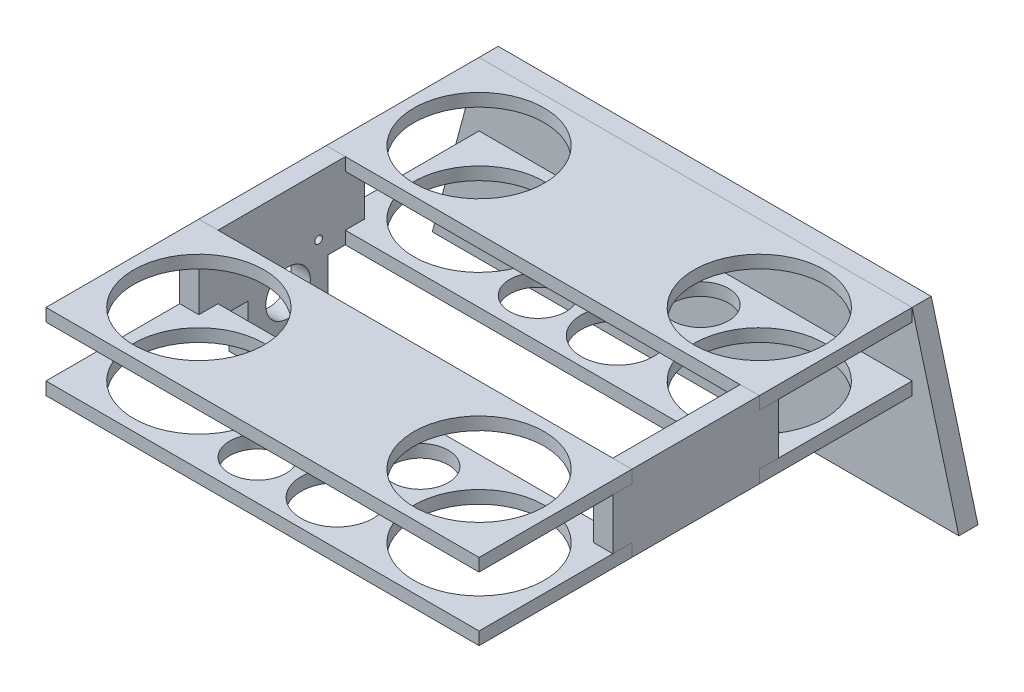
SolidWorks part; units mm, degrees
material "Alum Plate"
ref_plane "Front Plane" through (0, 0, 0) normal (0, 0, 1) x (1, 0, 0)
ref_plane "Top Plane" through (0, 0, 0) normal (0, 1, 0) x (1, 0, 0)
ref_plane "Right Plane" through (0, 0, 0) normal (1, 0, 0) x (0, 0, -1)
sketch "Sketch1" plane through (0, 0, 0) normal (0, 1, 0) x (1, 0, 0)
  line L0 (-69.85, 69.85) -> (-14.9491, 85.725) construction
  line L1 (107.95, -107.95) -> (-107.95, -107.95)
  line L2 (107.95, -107.95) -> (107.95, 107.95)
  line L3 (107.95, 107.95) -> (-107.95, 107.95)
  line L4 (-107.95, -107.95) -> (-107.95, 107.95)
  line L5 (107.95, -107.95) -> (-107.95, 107.95) construction
  line L6 (107.95, 107.95) -> (-107.95, -107.95) construction
  line L7 (-14.9491, 85.725) -> (-22.225, 51.5663) construction
  line L8 (-127, 0) -> (49.8373, 0) construction
  line L9 (0, 0) -> (0, 61.2225) construction
  line L10 (-107.95, 31.75) -> (107.95, 31.75) construction
  line L11 (-104.775, -14.825) -> (-47.625, -14.825)
  line L12 (-104.775, -14.825) -> (-104.775, 21.175)
  line L13 (-104.775, 21.175) -> (-47.625, 21.175)
  line L14 (-47.625, -14.825) -> (-47.625, 21.175)
  line L15 (-104.775, -14.825) -> (-47.625, 21.175) construction
  line L16 (-104.775, 21.175) -> (-47.625, -14.825) construction
  line L17 (-47.625, -10.825) -> (-0.635, -10.825)
  line L18 (-47.625, -10.825) -> (-47.625, 17.175)
  line L19 (-47.625, 17.175) -> (-0.635, 17.175)
  line L20 (-0.635, -10.825) -> (-0.635, 17.175)
  line L21 (-47.625, -10.825) -> (-0.635, 17.175) construction
  line L22 (-47.625, 17.175) -> (-0.635, -10.825) construction
  line L23 (-69.85, 31.75) -> (-69.85, 69.85) construction
  line L24 (-69.85, 69.85) -> (-69.85, 107.95) construction
  circle A0 centre (-69.85, 69.85) radius 32.5
  circle A1 centre (-14.9491, 85.725) radius 18
  circle A2 centre (-22.225, 51.5663) radius 14
  point P2 (0, 0)
  point P15 (-76.2, 3.175)
  point P21 (-69.85, 102.35)
  point P22 (-24.13, 3.175)
  point P27 (-69.85, 37.35)
  point P28 (-14.9491, 67.725)
  point P29 (-47.625, 3.175)
  point P30 (-14.9491, 103.725)
  point P31 (-22.225, 65.5663)
  point P32 (-22.225, 37.5663)
  point P37 (-76.2, 10.0231)
  dimension "D1" = 65
  dimension "D6" = 28
  dimension "D7" = 36
  dimension "D2" = 38.1
  dimension "D3" = 38.1
  dimension "D4" = 215.9
  dimension "D5" = 22.225
  dimension "D8" = 57.15
  dimension "D9" = 34.925
  dimension "D10" = 22.225
  dimension "D11" = 36
  dimension "D12" = 57.15
  dimension "D13" = 46.99
  dimension "D14" = 28
  dimension "D15" = 28.575
  dimension "D16" = 3.175
sketch "Sketch2" plane through (0, 0, 0) normal (1, 0, 0) x (0, 0, -1)
  line L0 (-200000, 0) -> (200061.2225, 0) construction
  line L1 (69.85, 50.8) -> (69.85, 53.975) construction
  line L2 (37.35, 60.975) -> (102.35, 60.975)
  line L3 (37.35, 60.975) -> (37.35, 53.975)
  line L4 (37.35, 53.975) -> (102.35, 53.975)
  line L5 (102.35, 60.975) -> (102.35, 53.975)
  line L6 (37.35, 60.975) -> (102.35, 53.975) construction
  line L7 (37.35, 53.975) -> (102.35, 60.975) construction
  line L8 (37.35, 92.075) -> (102.35, 92.075)
  line L9 (37.35, 92.075) -> (37.35, 85.075)
  line L10 (37.35, 85.075) -> (102.35, 85.075)
  line L11 (102.35, 92.075) -> (102.35, 85.075)
  line L12 (37.35, 92.075) -> (102.35, 85.075) construction
  line L13 (37.35, 85.075) -> (102.35, 92.075) construction
  line L14 (67.5868, 73.025) -> (88.6392, 73.025) construction
  line L15 (69.85, 60.975) -> (69.85, 73.025) construction
  line L16 (69.85, 73.025) -> (69.85, 85.075) construction
  circle A0 centre (69.85, 25.4) radius 25.4
  circle A1 centre (3.175, 47.625) radius 18
  point P4 (69.85, 57.475)
  point P9 (69.85, 88.575)
  point P25 (-14.825, 47.625)
  point P26 (21.175, 47.625)
  point P27 (0, 0)
  point P29 (0, 0)
  point P31 (0, 0)
  point P32 (19.05, 35.9954)
  dimension "D1" = 50.8
  dimension "D2" = 7
  dimension "D3" = 3.175
  dimension "D4" = 38.1
  dimension "D5" = 6.35
ref_plane "Plane1" through (0, 53.975, 0) normal (0, 1, 0) x (1, 0, 0)
sketch "Sketch3" plane through (0, 53.975, 0) normal (0, 1, 0) x (1, 0, 0)
  line L0 (0, -200000) -> (0, 200061.2225) construction
  line L1 (-107.95, 107.95) -> (0, 107.95)
  line L2 (-107.95, 107.95) -> (-107.95, 31.75)
  line L3 (-107.95, 31.75) -> (0, 31.75)
  line L4 (0, 107.95) -> (0, 31.75)
  line L5 (-107.95, 107.95) -> (0, 31.75) construction
  line L6 (-107.95, 31.75) -> (0, 107.95) construction
  line L7 (-107.95, 69.85) -> (-69.85, 69.85) construction
  circle A0 centre (-69.85, 69.85) radius 32.5 construction
  circle A1 centre (-69.85, 69.85) radius 32.5
  point P7 (-53.975, 69.85)
extrude "Boss-Extrude1" add sketch "Sketch3" along normal blind 6.35
ref_plane "Plane2" through (0, 73.025, 0) normal (0, 1, 0) x (1, 0, 0)
mirror "Mirror1" about plane through (0, 73.025, 0) normal (0, 1, 0) of bodies 101
mirror "Mirror2" about plane through (0, 0, 0) normal (1, 0, 0) of bodies 101 102 114
sketch "Sketch5" plane through (0, 60.325, 0) normal (0, 1, 0) x (1, 0, 0)
  circle A0 centre (-22.225, 51.5663) radius 14 construction
  circle A1 centre (-14.9491, 85.725) radius 18 construction
  circle A2 centre (-22.225, 51.5663) radius 14
  circle A3 centre (-14.9491, 85.725) radius 18
  point P6 (0, 69.85)
extrude "Cut-Extrude1" cut sketch "Sketch5" against normal through all
ref_axis "Axis1" through (0, 60.975, -69.85) along (0, 1, 0)
pattern_circular "CirPattern1" count 2 over 360 about axis through (0, 60.975, -69.85) along (0, 1, 0) of "Cut-Extrude1"
ref_axis "Axis2" through (0, -4.6038, 0) along (0, 1, 0)
pattern_circular "CirPattern2" count 2 over 360 about axis through (0, -4.6038, 0) along (0, 1, 0) of bodies 104 108
sketch "Sketch6" plane through (-107.95, 0, 0) normal (-1, 0, 0) x (0, 0, 1)
  line L0 (-38.1, 60.325) -> (-38.1, 85.725)
  line L1 (-107.95, 60.325) -> (-31.75, 60.325) construction
  line L2 (-107.95, 85.725) -> (-31.75, 85.725) construction
  line L3 (-38.1, 85.725) -> (-31.75, 85.725)
  line L4 (-31.75, 85.725) -> (-31.75, 92.075)
  line L5 (-31.75, 92.075) -> (31.75, 92.075)
  line L6 (31.75, 92.075) -> (31.75, 85.725)
  line L7 (31.75, 85.725) -> (38.1, 85.725)
  line L8 (107.95, 85.725) -> (31.75, 85.725) construction
  line L9 (38.1, 85.725) -> (38.1, 60.325)
  line L10 (107.95, 60.325) -> (31.75, 60.325) construction
  line L11 (38.1, 60.325) -> (31.75, 60.325)
  line L12 (31.75, 60.325) -> (31.75, 53.975)
  line L13 (31.75, 53.975) -> (-31.75, 53.975)
  line L14 (-31.75, 53.975) -> (-31.75, 60.325)
  line L15 (-31.75, 60.325) -> (-38.1, 60.325)
  point P6 (31.75, 60.325)
  point P29 (31.75, 85.725)
  dimension "D1" = 6.35
sketch "Sketch9" plane through (0, 0, -107.95) normal (0, 0, -1) x (-1, 0, 0)
  line L0 (-107.95, 92.075) -> (-131.2602, 5.08)
  line L1 (-131.2602, 5.08) -> (131.2602, 5.08)
  line L2 (131.2602, 5.08) -> (107.95, 92.075)
  line L3 (107.95, 92.075) -> (-107.95, 92.075)
  line L5 (200127, 0) -> (-200049.8373, 0) construction
  line L6 (-107.95, 60.325) -> (-107.95, 53.975) construction
  dimension "D1" = 15
  dimension "D2" = 5.08
extrude "Boss-Extrude5" add sketch "Sketch9" along normal blind 9.525 separate body
sketch "Sketch11" plane through (-107.95, 0, 0) normal (-1, 0, 0) x (0, 0, 1)
  line L0 (-31.75, 53.975) -> (-31.75, 60.325)
  line L1 (-31.75, 60.325) -> (-41.275, 60.325)
  line L2 (-41.275, 60.325) -> (-41.275, 85.725)
  line L3 (-107.95, 85.725) -> (-31.75, 85.725) construction
  line L4 (-41.275, 85.725) -> (-31.75, 85.725)
  line L5 (-31.75, 85.725) -> (-31.75, 92.075)
  line L6 (-31.75, 92.075) -> (31.75, 92.075)
  line L7 (31.75, 92.075) -> (31.75, 85.725)
  line L8 (31.75, 85.725) -> (41.275, 85.725)
  line L9 (41.275, 85.725) -> (41.275, 60.325)
  line L10 (107.95, 60.325) -> (31.75, 60.325) construction
  line L11 (41.275, 60.325) -> (31.75, 60.325)
  line L12 (31.75, 60.325) -> (31.75, 53.975)
  line L13 (31.75, 53.975) -> (-31.75, 53.975)
  dimension "D1" = 9.525
extrude "Boss-Extrude7" add sketch "Sketch11" against normal blind 9.525 separate body
mirror "Mirror7" about plane through (0, 0, 0) normal (1, 0, 0) of bodies 121
sketch "Sketch10" plane through (-107.95, 0, 0) normal (-1, 0, 0) x (0, 0, 1)
  line L1 (-23.1775, 67.6275) -> (16.8275, 67.6275)
  line L2 (-23.1775, 67.6275) -> (-23.1775, 27.6225)
  line L3 (-23.1775, 27.6225) -> (16.8275, 27.6225)
  line L4 (16.8275, 67.6275) -> (16.8275, 27.6225)
  line L5 (-23.1775, 67.6275) -> (16.8275, 27.6225) construction
  line L6 (-23.1775, 27.6225) -> (16.8275, 67.6275) construction
  point P0 (-3.175, 47.625)
  dimension "D1" = 40.005
extrude "Boss-Extrude6" add sketch "Sketch10" against normal up to surface (9.525 mm away) up to face at (-98.425, 73.025, 0)
sketch "Sketch12" plane through (-107.95, 0, 0) normal (-1, 0, 0) x (0, 0, 1)
  line L1 (-18.415, 62.865) -> (12.065, 62.865) construction
  line L2 (-18.415, 62.865) -> (-18.415, 32.385) construction
  line L3 (-18.415, 32.385) -> (12.065, 32.385) construction
  line L4 (12.065, 62.865) -> (12.065, 32.385) construction
  line L5 (-18.415, 62.865) -> (12.065, 32.385) construction
  line L6 (-18.415, 32.385) -> (12.065, 62.865) construction
  circle A0 centre (-18.415, 62.865) radius 1.905
  circle A1 centre (12.065, 62.865) radius 1.905
  circle A2 centre (12.065, 32.385) radius 1.905
  circle A3 centre (-18.415, 32.385) radius 1.905
  circle A4 centre (-3.175, 47.625) radius 11.1125
  point P0 (-3.175, 47.625)
  dimension "D2" = 3.81
  dimension "D3" = 22.225
  dimension "D1" = 30.48
extrude "Cut-Extrude2" cut sketch "Sketch12" against normal through all
